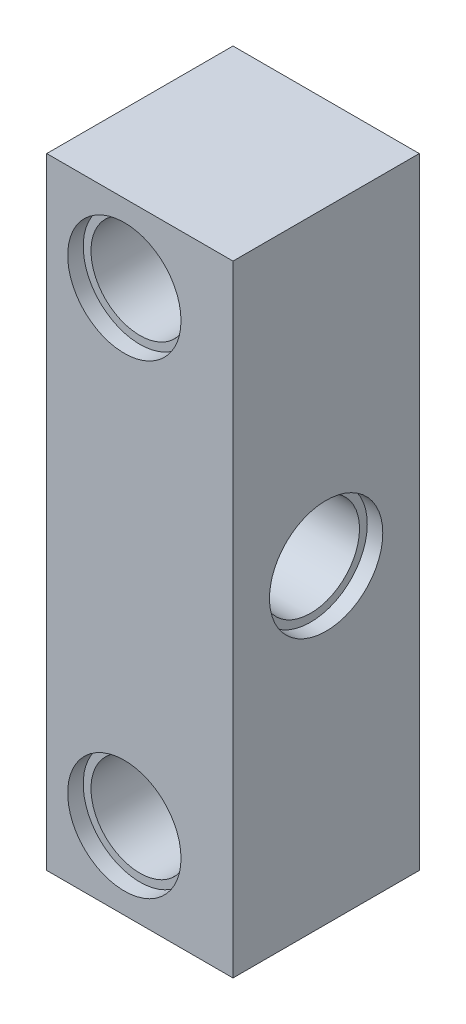
SolidWorks part; units mm, degrees
ref_plane "Front" through (0, 0, 0) normal (0, 0, 1) x (1, 0, 0)
ref_plane "Top" through (0, 0, 0) normal (0, 1, 0) x (1, 0, 0)
ref_plane "Right" through (0, 0, 0) normal (1, 0, 0) x (0, 0, -1)
sketch "Esquisse1" plane through (0, 0, 0) normal (0, 0, 1) x (1, 0, 0)
  line L1 (0, 0) -> (12, 0)
  line L2 (0, 0) -> (0, 40)
  line L3 (0, 40) -> (12, 40)
  line L4 (12, 0) -> (12, 40)
  dimension "D1" = 12
  dimension "D2" = 40
extrude "Boss.-Extru.1" add sketch "Esquisse1" along normal blind 12
sketch "Esquisse3" plane through (0, 0, 12) normal (0, 0, 1) x (1, 0, 0)
  line L0 (5, 40) -> (5, 0) construction
  line L2 (0, 0) -> (12, 0) construction
  line L3 (12, 40) -> (0, 40) construction
  line L4 (0, 40) -> (0, 0) construction
  circle A0 centre (5, 5) radius 3.15
  circle A1 centre (5, 35) radius 3.15
  dimension "D1" = 30
  dimension "D2" = 5
  dimension "D3" = 6.3
  dimension "D4" = 5
extrude "Enlèv. mat.-Extru.1" cut sketch "Esquisse3" against normal through all both and the other way through all
sketch "Esquisse4" plane through (12, 0, 0) normal (1, 0, 0) x (0, 0, -1)
  line L0 (-6, 0) -> (-6, 40) construction
  line L1 (-12, 0) -> (0, 0) construction
  line L2 (-12, 40) -> (0, 40) construction
  circle A0 centre (-6, 20) radius 3.15
  dimension "D1" = 6.3
extrude "Enlèv. mat.-Extru.2" cut sketch "Esquisse4" against normal through all both and the other way through all
sketch "Esquisse5" plane through (0, 0, 12) normal (0, 0, 1) x (1, 0, 0)
  circle A0 centre (5, 35) radius 3.65
  circle A1 centre (5, 5) radius 3.65
  dimension "D1" = 7.3
extrude "Enlèv. mat.-Extru.3" cut sketch "Esquisse5" against normal blind 1
sketch "Esquisse6" plane through (12, 0, 0) normal (1, 0, 0) x (0, 0, -1)
  circle A0 centre (-6, 20) radius 3.65
  dimension "D1" = 7.3
extrude "Enlèv. mat.-Extru.4" cut sketch "Esquisse6" against normal blind 1
sketch "Esquisse7" [suppressed] plane through (12, 0, 0) normal (1, 0, 0) x (0, 0, -1)
  line L1 (-12, 0) -> (-12, 40) construction
  line L2 (0, 0) -> (-12, 0)
  line L3 (0, 0) -> (0, -8)
  line L4 (0, -8) -> (-12, -8)
  line L5 (-12, 0) -> (-12, -8)
  line L6 (-12, 20) -> (0, 20) construction
  line L7 (0, 0) -> (0, 40) construction
  line L8 (-12, 40) -> (-12, 48)
  line L9 (0, 48) -> (-12, 48)
  line L10 (0, 40) -> (0, 48)
  line L11 (0, 40) -> (-12, 40)
  dimension "D1" = 8
extrude "Boss.-Extru.2" [suppressed] add sketch "Esquisse7" against normal up to vertex up to point (0, 0, 0)
sketch "Esquisse8" [suppressed] plane through (0, -8, 0) normal (0, -1, 0) x (1, 0, 0)
  line L0 (0, 12) -> (12, 12) construction
  line L1 (12, 0) -> (11, 0)
  line L2 (12, 0) -> (12, 12)
  line L3 (12, 12) -> (11, 12)
  line L4 (11, 0) -> (11, 12)
  dimension "D1" = 1
extrude "Enlèv. mat.-Extru.5" [suppressed] cut sketch "Esquisse8" against normal through all both and the other way through all
sketch "Esquisse9" [suppressed] plane through (11, 0, 0) normal (1, 0, 0) x (0, 0, -1)
  line L0 (-12, 20) -> (0, 20) construction
  line L1 (-12, 48) -> (-12, -8) construction
  line L2 (0, 48) -> (0, -8) construction
  line L3 (-6, 20) -> (-6, 42) construction
  circle A0 centre (-6, 42) radius 3.15
  circle A1 centre (-6, 20) radius 3.15 construction
  circle A2 centre (-6, -2) radius 3.15
  dimension "D1" = 22
extrude "Enlèv. mat.-Extru.6" [suppressed] cut sketch "Esquisse9" against normal through all both and the other way through all
sketch "Esquisse10" [suppressed] plane through (0, 0, 0) normal (-1, 0, 0) x (0, 0, 1)
  circle A0 centre (6, 42) radius 3.65
  circle A1 centre (6, -2) radius 3.65
  circle A2 centre (6, 20) radius 3.65
  dimension "D1" = 7.3
extrude "Enlèv. mat.-Extru.7" [suppressed] cut sketch "Esquisse10" against normal blind 1
